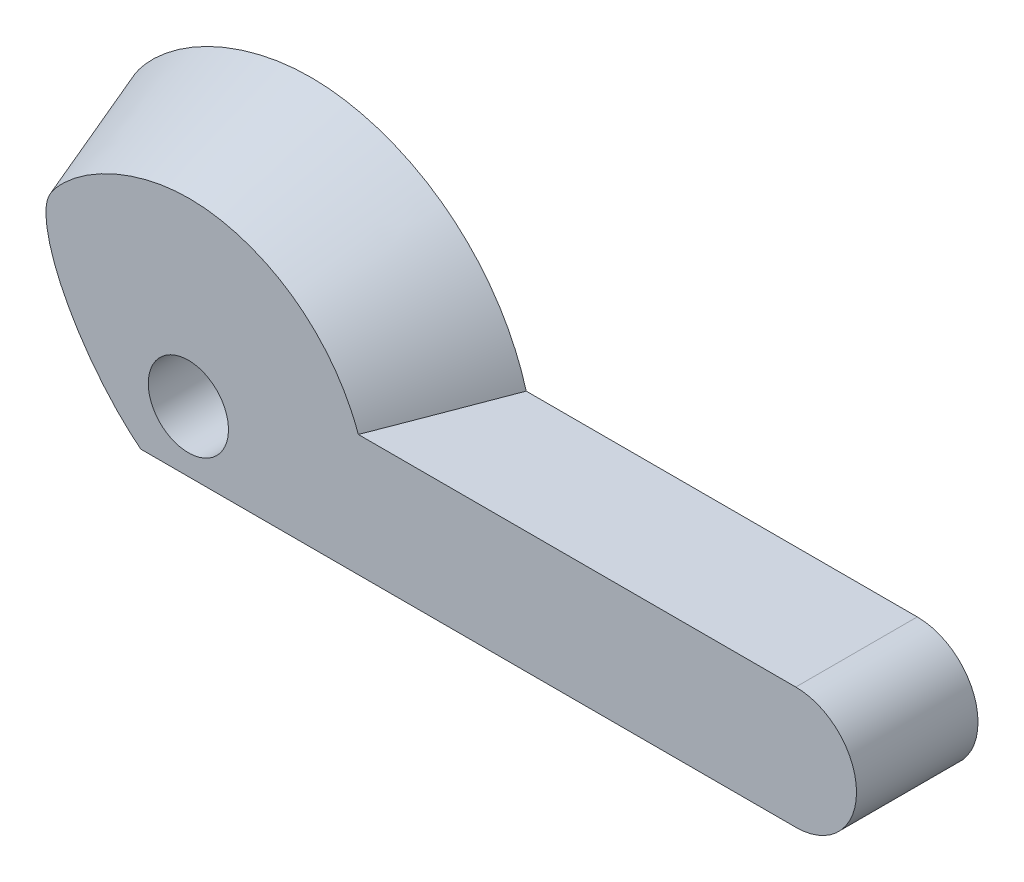
SolidWorks part; units mm, degrees
ref_plane "Plano frontal" through (0, 0, 0) normal (0, 0, 1) x (1, 0, 0)
ref_plane "Plano superior" through (0, 0, 0) normal (0, 1, 0) x (1, 0, 0)
ref_plane "Plano direito" through (0, 0, 0) normal (1, 0, 0) x (0, 0, -1)
sketch "Esboço2" plane through (0, 0, 0) normal (0, 0, 1) x (1, 0, 0)
  line L0 (25, 2.5) -> (8.9058, 2.5)
  line L1 (25, -2.5) -> (4.3301, -2.5)
  line L2 (0, 0) -> (-3.2897, -3.7653) construction
  line L3 (0, 0) -> (-3.7653, 3.2897) construction
  line L5 (-4.5184, 3.9477) -> (-6.9659, 6.086) construction
  arc A0 (25, -2.5) -> (25, 2.5) centre (25, 0) ccw
  circle A1 centre (0, 0) radius 1.65
  circle A2 centre (0, 0) radius 5 construction
  circle A3 centre (0, 0) radius 9.25 construction
  spline S0 degree 3 poles (4.3301, -2.5) (3.6274, -3.6971) (1.501, -5.3032) (-1.714, -4.9157) (-5.419, -2.304) (-9.0198, 3.4922) (-5.6751, 7.7775) (-1.7732, 9.5205) (2.2606, 9.1278) (6.2171, 7.429) (8.2601, 4.7846) (8.9058, 2.5) knots 0 0 0 0 0.103912 0.19054 0.222509 0.458861 0.503374 0.667648 0.751689 0.822132 1 1 1 1
  dimension "D1" = 3.3
  dimension "D2" = 10
  dimension "D3" = 18.5
  dimension "D4" = 2.5
  dimension "D5" = 25
extrude "Ressalto-extrusão1" add sketch "Esboço2" along normal blind 5
chamfer "Chanfro1" distance 5 angle 20 1 edges
sketch "Esboço3" plane through (0, 0, 5) normal (0, 0, 1) x (1, 0, 0)
  line L0 (1.9625, -2.5) -> (25, -2.5) construction
  line L1 (7.7033, -2.5) -> (-9.1181, -2.5)
  line L2 (7.7033, -2.5) -> (7.7033, -6.3348)
  line L3 (7.7033, -6.3348) -> (-9.1181, -6.3348)
  line L4 (-9.1181, -2.5) -> (-9.1181, -6.3348)
extrude "Corte-extrusão1" cut sketch "Esboço3" against normal blind 5
mirror "Espelhar3" about plane through (0, 0, 0) normal (0, 0, 1) of bodies 102
sketch "Esboço4" plane through (0, 0, 0) normal (0, 0, 1) x (1, 0, 0)
  line L1 (-59.921, -16.1439) -> (59.921, -16.1439)
  line L2 (-59.921, -16.1439) -> (-59.921, 16.1439)
  line L3 (-59.921, 16.1439) -> (59.921, 16.1439)
  line L4 (59.921, -16.1439) -> (59.921, 16.1439)
  line L5 (-59.921, -16.1439) -> (59.921, 16.1439) construction
  line L6 (-59.921, 16.1439) -> (59.921, -16.1439) construction
  point P0 (0, 0)
extrude "Corte-extrusão2" cut sketch "Esboço4" along normal blind 10
